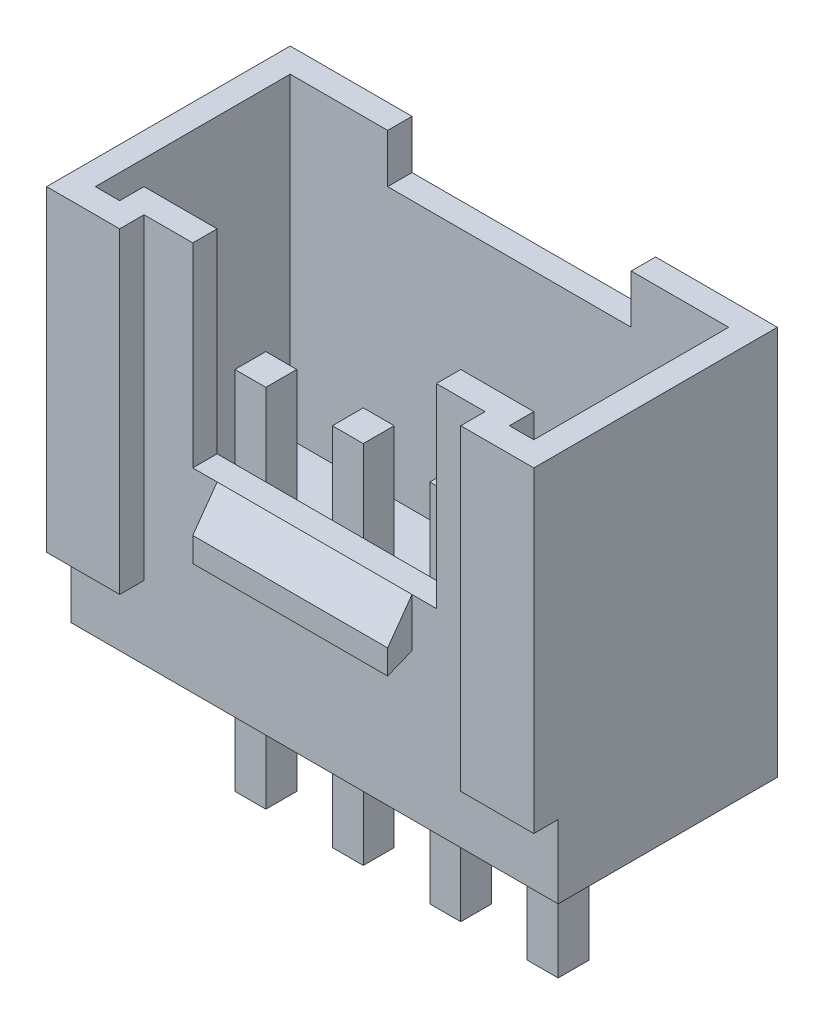
SolidWorks part; units mm, degrees
ref_plane "Front Plane" through (0, 0, 0) normal (0, 0, 1) x (1, 0, 0)
ref_plane "Top Plane" through (0, 0, 0) normal (0, 1, 0) x (1, 0, 0)
ref_plane "Right Plane" through (0, 0, 0) normal (1, 0, 0) x (0, 0, -1)
sketch "Sketch1" plane through (0, 0, 0) normal (0, 1, 0) x (1, 0, 0)
  line L0 (8.5, 0) -> (10, 0)
  line L1 (0, 0) -> (1.5, 0)
  line L2 (0, 0) -> (0, 5)
  line L3 (0, 5) -> (10, 5)
  line L4 (10, 0) -> (10, 5)
  line L6 (1.5, 0) -> (1.5, 0.5)
  line L7 (1.5, 0.5) -> (8.5, 0.5)
  line L8 (8.5, 0) -> (8.5, 0.5)
  line L10 (0.5, 4.5) -> (9.5, 4.5)
  line L11 (0.5, 4.5) -> (0.5, 1.5385)
  line L12 (1, 1) -> (9, 1)
  line L13 (9.5, 4.5) -> (9.5, 1.5288)
  line L15 (9.5, 1.5288) -> (9.5, 0.5)
  line L16 (9.5, 0.5) -> (9, 0.5)
  line L17 (9, 1) -> (9, 0.5)
  line L19 (0.5, 1.5385) -> (0.5, 0.5)
  line L20 (0.5, 0.5) -> (1, 0.5)
  line L21 (1, 1) -> (1, 0.5)
  point P9 (5, 0.5)
  point P10 (5, 5)
  point P21 (10, 2.5)
  dimension "D1" = 0.5
  dimension "D2" = 0.5
  dimension "D3" = 0.5
  dimension "D4" = 0.5
  dimension "D5" = 0.5
  dimension "D6" = 0.5
  dimension "D7" = 10
  dimension "D8" = 5
  dimension "D9" = 0.5
  dimension "D10" = 1
extrude "Sides" add sketch "Sketch1" along normal blind 8
sketch "Sketch2" plane through (0, 0, -0.5) normal (0, 0, 1) x (1, 0, 0)
  line L0 (1.5, 8) -> (8.5, 8) construction
  line L1 (2.5, 8) -> (7.5, 8)
  line L2 (2.5, 8) -> (2.5, 4)
  line L3 (2.5, 4) -> (7.5, 4)
  line L4 (7.5, 8) -> (7.5, 4)
  line L5 (1.5, 0) -> (8.5, 0) construction
  point P6 (5, 8)
  point P9 (5, 0)
  dimension "D1" = 4
  dimension "D2" = 5
extrude "Front cut" cut sketch "Sketch2" against normal up to surface (0.5 mm away) up to face at (5, 4, -1)
sketch "Sketch3" plane through (0, 0, -5) normal (0, 0, -1) x (-1, 0, 0)
  line L0 (-10, 8) -> (0, 8) construction
  line L1 (-2.5, 8) -> (-7.5, 8)
  line L2 (-2.5, 8) -> (-2.5, 7)
  line L3 (-2.5, 7) -> (-7.5, 7)
  line L4 (-7.5, 8) -> (-7.5, 7)
  line L5 (-10, 0) -> (0, 0) construction
  point P6 (-5, 8)
  point P9 (-5, 0)
  dimension "D1" = 5
  dimension "D2" = 1
extrude "Back cut" cut sketch "Sketch3" against normal up to next
extrude "Base" add sketch "Sketch1<2>" along normal blind 0.5 contours L21 L12 L17 L16 L15 L13 L10 L11 L19 L20 region at (5, 0, -2.7188)
sketch "Sketch1<2>" plane through (0, 0, 0) normal (0, 1, 0) x (1, 0, 0) same geometry as "Sketch1"
sketch "Sketch4" plane through (0, 0.5, 0) normal (0, 1, 0) x (1, 0, 0)
  line L0 (0.5, 4.5) -> (0.5, 0.5) construction
  line L1 (1.6825, 2.8175) -> (2.3175, 2.8175)
  line L2 (1.6825, 2.8175) -> (1.6825, 2.1825)
  line L3 (1.6825, 2.1825) -> (2.3175, 2.1825)
  line L4 (2.3175, 2.8175) -> (2.3175, 2.1825)
  line L5 (3.6825, 2.8175) -> (3.6825, 2.1825)
  line L6 (3.6825, 2.8175) -> (4.3175, 2.8175)
  line L7 (4.3175, 2.8175) -> (4.3175, 2.1825)
  line L8 (3.6825, 2.1825) -> (4.3175, 2.1825)
  line L9 (5.6825, 2.8175) -> (5.6825, 2.1825)
  line L10 (5.6825, 2.8175) -> (6.3175, 2.8175)
  line L11 (6.3175, 2.8175) -> (6.3175, 2.1825)
  line L12 (5.6825, 2.1825) -> (6.3175, 2.1825)
  line L13 (7.6825, 2.8175) -> (7.6825, 2.1825)
  line L14 (7.6825, 2.8175) -> (8.3175, 2.8175)
  line L15 (8.3175, 2.8175) -> (8.3175, 2.1825)
  line L16 (7.6825, 2.1825) -> (8.3175, 2.1825)
  line L17 (1.6825, 2.8175) -> (3.6825, 2.8175) construction
  line L18 (1.6825, 2.5) -> (8.3175, 2.5) construction
  line L19 (2.5, 1) -> (7.5, 1) construction
  point P6 (0.5, 2.5)
  point P7 (2.3175, 2.5)
  point P24 (5, 2.5)
  point P27 (5, 1)
  dimension "D1" = 0.635
  dimension "D3" = 2
  dimension "D2" = 4
extrude "Pins" add sketch "Sketch4" along normal blind 4 and the other way blind 3.5
ref_plane "Plane1" through (5, 0, 0) normal (1, 0, 0) x (0, 0, -1)
sketch "Sketch5" plane through (5, 0, 0) normal (1, 0, 0) x (0, 0, -1)
  line L0 (0.5, 4) -> (0.5, 3)
  line L1 (0.5, 3) -> (0, 2.8)
  line L2 (0, 2.8) -> (0, 3.3)
  line L3 (0, 3.3) -> (0.5, 4)
  dimension "D1" = 0.5
  dimension "D2" = 0.5
  dimension "D3" = 1.2
  dimension "D4" = 1
extrude "Clip" add sketch "Sketch5" along normal blind 2 and the other way blind 2
sketch "Sketch6" plane through (5, 0, 0) normal (1, 0, 0) x (0, 0, -1)
  line L1 (0, 0) -> (0.5, 0)
  line L2 (0, 0) -> (0, 1.5)
  line L3 (0, 1.5) -> (0.5, 1.5)
  line L4 (0.5, 0) -> (0.5, 1.5)
  dimension "D1" = 0.5
  dimension "D2" = 1.5
extrude "Front trim" cut sketch "Sketch6" against normal through all both and the other way through all
extrude "Boss-Extrude4" add sketch "Sketch1<4>" along normal blind 1.51 contours L21 L12 L17 L16 L15 L13 L10 L11 L19 L20 region at (5, 0, -2.7188)
sketch "Sketch1<4>" plane through (0, 0, 0) normal (0, 1, 0) x (1, 0, 0) same geometry as "Sketch1"
